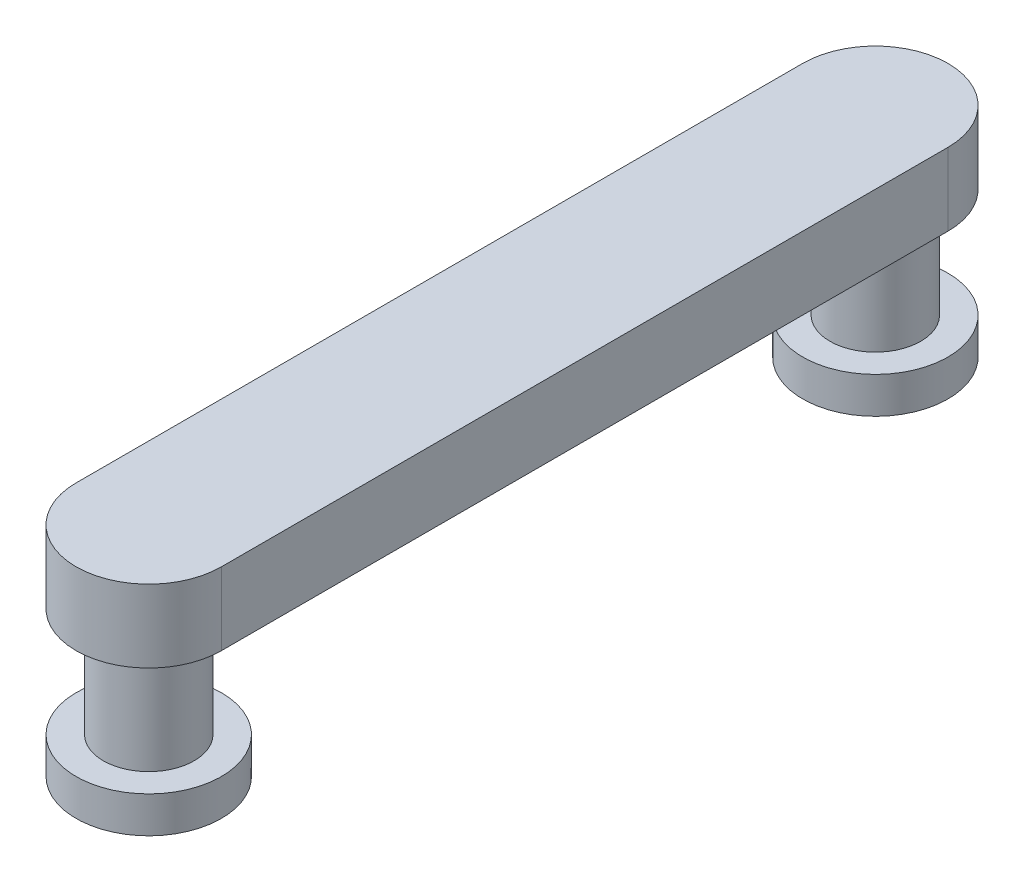
SolidWorks part; units mm, degrees
ref_plane "Front Plane" through (0, 0, 0) normal (0, 0, 1) x (1, 0, 0)
ref_plane "Top Plane" through (0, 0, 0) normal (0, 1, 0) x (1, 0, 0)
ref_plane "Right Plane" through (0, 0, 0) normal (1, 0, 0) x (0, 0, -1)
sketch "Sketch1" plane through (0, 0, 0) normal (0, 1, 0) x (1, 0, 0)
  line L0 (0, 0) -> (0, 25.4)
  line L1 (0, 0) -> (0, -25.4)
  line L4 (-5.08, 25.4) -> (-5.08, -25.4)
  line L5 (5.08, -25.4) -> (5.08, 25.4)
  arc A0 (5.08, 25.4) -> (-5.08, 25.4) centre (0, 25.4) ccw
  arc A1 (-5.08, -25.4) -> (5.08, -25.4) centre (0, -25.4) ccw
sketch "Sketch2" plane through (0, 0, 0) normal (0, 1, 0) x (1, 0, 0)
  line L0 (-5.08, 25.4) -> (-5.08, -25.4)
  line L1 (5.08, -25.4) -> (5.08, 25.4)
  arc A0 (5.08, 25.4) -> (-5.08, 25.4) centre (0, 25.4) ccw
  arc A1 (-5.08, -25.4) -> (5.08, -25.4) centre (0, -25.4) ccw
extrude "Boss-Extrude1" add sketch "Sketch2" along normal blind 5.08
sketch "Sketch3" plane through (0, 0, 0) normal (0, -1, 0) x (-1, 0, 0)
  circle A0 centre (0, -25.4) radius 3.175
  circle A1 centre (0, 25.4) radius 3.175
extrude "Boss-Extrude2" add sketch "Sketch3" along normal blind 7.62
sketch "Sketch5" plane through (0, -7.62, 0) normal (0, -1, 0) x (1, 0, 0)
  circle A0 centre (0, 25.4) radius 5.08
sketch "Sketch6" plane through (0, -7.62, 0) normal (0, -1, 0) x (1, 0, 0)
  circle A0 centre (0, 25.4) radius 5.08
extrude "Boss-Extrude3" add sketch "Sketch6" along normal blind 2.54
sketch "Sketch7" plane through (0, -7.62, 0) normal (0, -1, 0) x (1, 0, 0)
  circle A0 centre (0, -25.4) radius 5.08
sketch "Sketch8" plane through (0, -7.62, 0) normal (0, -1, 0) x (1, 0, 0)
  circle A0 centre (0, -25.4) radius 5.08
extrude "Boss-Extrude4" add sketch "Sketch8" along normal blind 2.54
